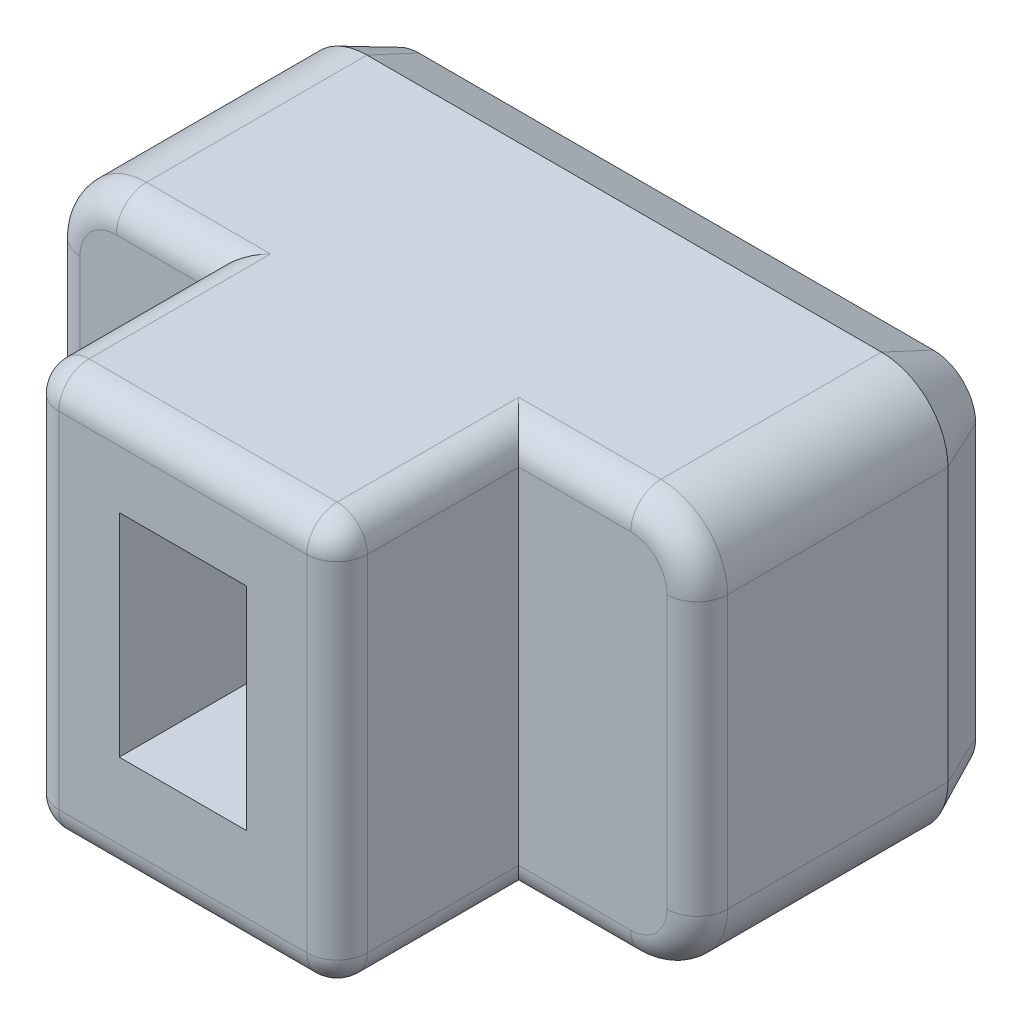
SolidWorks part; units mm, degrees
ref_plane "Plan de face" through (0, 0, 0) normal (0, 0, 1) x (1, 0, 0)
ref_plane "Plan de dessus" through (0, 0, 0) normal (0, 1, 0) x (1, 0, 0)
ref_plane "Plan de droite" through (0, 0, 0) normal (1, 0, 0) x (0, 0, -1)
sketch "Esquisse2" plane through (0, 0, 0) normal (0, 0, 1) x (1, 0, 0)
  line L1 (1.1, 0) -> (9.6, 0)
  line L2 (0, 1.1) -> (0, 5.6)
  line L3 (1.1, 6.7) -> (9.6, 6.7)
  line L4 (10.7, 1.1) -> (10.7, 5.6)
  arc A0 (9.6, 6.7) -> (10.7, 5.6) centre (9.6, 5.6) cw
  arc A1 (9.6, 0) -> (10.7, 1.1) centre (9.6, 1.1) ccw
  arc A2 (1.1, 0) -> (0, 1.1) centre (1.1, 1.1) cw
  arc A3 (0, 5.6) -> (1.1, 6.7) centre (1.1, 5.6) cw
  point P7 (10.7, 6.7)
  point P12 (0, 0)
  point P15 (0, 6.7)
  dimension "D3" = 1.1
  dimension "D1" = 10.7
  dimension "D2" = 6.7
extrude "Boss.-Extru.1" add sketch "Esquisse2" along normal blind 8
sketch "Esquisse3" plane through (0, 0, 8) normal (0, 0, 1) x (1, 0, 0)
  line L0 (0, 5.6) -> (0, 1.1) construction
  line L1 (4.15, 5.25) -> (6.25, 5.25)
  line L2 (4.15, 5.25) -> (4.15, 1.75)
  line L3 (4.15, 1.75) -> (6.25, 1.75)
  line L4 (6.25, 5.25) -> (6.25, 1.75)
  line L5 (10.7, 1.1) -> (10.7, 5.6) construction
  line L6 (9.6, 6.7) -> (1.1, 6.7) construction
  line L7 (1.1, 0) -> (9.6, 0) construction
  dimension "D1" = 2.1
  dimension "D2" = 3.5
  dimension "D3" = 4.15
  dimension "D4" = 4.45
  dimension "D5" = 1.45
  dimension "D6" = 1.75
extrude "Enlèv. mat.-Extru.1" cut sketch "Esquisse3" against normal blind 3
sketch "Esquisse4" plane through (0, 0, 8) normal (0, 0, 1) x (1, 0, 0)
  line L0 (2.65, 6.7) -> (2.65, 0)
  line L1 (9.6, 6.7) -> (1.1, 6.7) construction
  line L2 (1.1, 0) -> (9.6, 0) construction
  line L3 (2.65, 0) -> (7.75, 0)
  line L4 (7.75, 0) -> (7.75, 6.7)
  line L5 (7.75, 6.7) -> (2.65, 6.7)
  line L6 (4.15, 5.25) -> (4.15, 1.75) construction
  line L7 (6.25, 1.75) -> (6.25, 5.25) construction
  dimension "D1" = 1.5
  dimension "D2" = 1.5
extrude "Enlèv. mat.-Extru.2" cut sketch "Esquisse4" against normal blind 3 flip side to cut
fillet "Congé1" radius 0.5 18 edges at (8.675, 0, 5) (10.3778, 0.3222, 5) (10.7, 3.35, 5) (10.3778, 6.3778, 5) (1.875, 6.7, 5) (0.3222, 6.3778, 5) (1.875, 0, 5) (0.3222, 0.3222, 5) (7.75, 6.7, 6.5) (2.65, 6.7, 6.5) (7.75, 0, 6.5) (2.65, 0, 6.5) (2.65, 3.35, 8) (5.2, 6.7, 8) (7.75, 3.35, 8) (5.2, 0, 8) (8.675, 6.7, 5) (0, 3.35, 5)
chamfer "Chanfrein1" distance 0.4 angle 65 8 edges at (5.35, 0, 0) (10.3778, 0.3222, 0) (0.3222, 0.3222, 0) (10.7, 3.35, 0) (0, 3.35, 0) (10.3778, 6.3778, 0) (0.3222, 6.3778, 0) (5.35, 6.7, 0) first distance on face at (5.35, 3.35, 0)
sketch "Esquisse5" plane through (0, 0, 0) normal (0, 0, 1) x (1, 0, 0)
  line L0 (-0.9378, 5.093) -> (11.6517, 5.093) construction
  text T0 "CDI" font "Corbel" height 3.5
extrude "Enlèv. mat.-Extru.3" cut sketch "Esquisse5" along normal blind 0.2
extrude "Boss.-Extru.2" add sketch "Esquisse5<4>" against normal blind 0.2
sketch "Esquisse5<4>" plane through (0, 0, 0) normal (0, 0, 1) x (1, 0, 0) same geometry as "Esquisse5"
